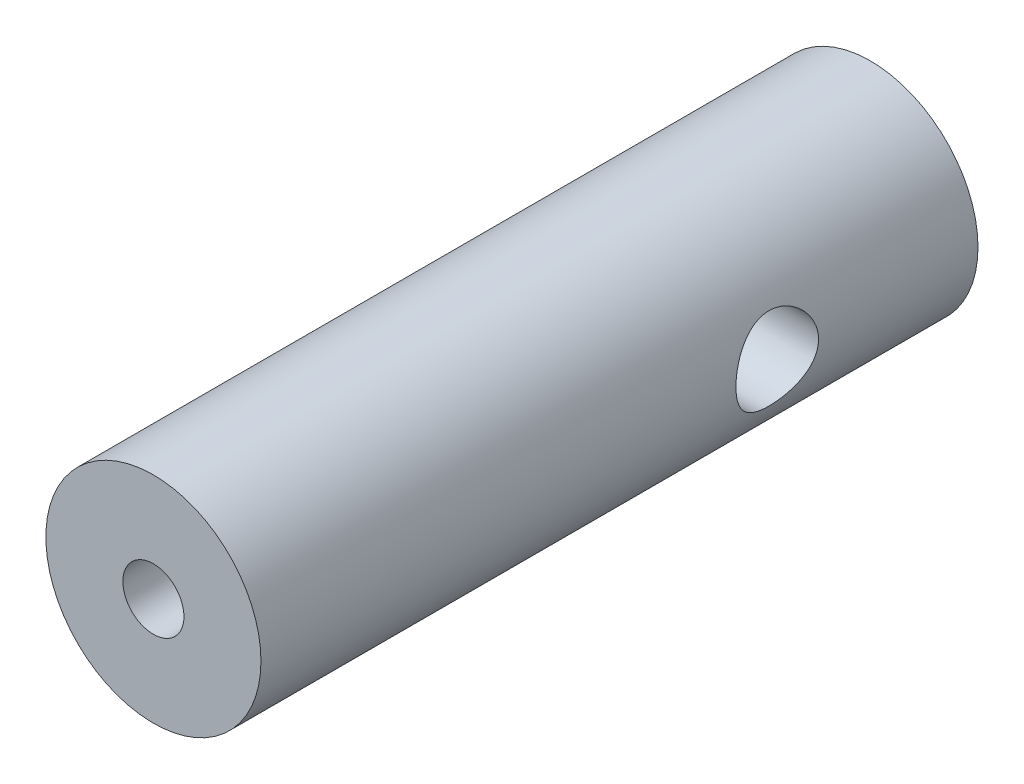
SolidWorks part; units mm, degrees
ref_plane "Front Plane" through (0, 0, 0) normal (0, 0, 1) x (1, 0, 0)
ref_plane "Top Plane" through (0, 0, 0) normal (0, 1, 0) x (1, 0, 0)
ref_plane "Right Plane" through (0, 0, 0) normal (1, 0, 0) x (0, 0, -1)
sketch "Sketch1" plane through (0, 0, 0) normal (0, 0, 1) x (1, 0, 0)
  circle A0 centre (0, 0) radius 4.7625
  dimension "D1" = 9.525
extrude "Boss-Extrude1" add sketch "Sketch1" along normal blind 31.75
sketch "Sketch2" plane through (0, 0, 31.75) normal (0, 0, 1) x (1, 0, 0)
  circle A0 centre (0, 0) radius 1.905
  dimension "D1" = 3.81
extrude "Cut-Extrude1" [suppressed] cut sketch "Sketch2" against normal blind 12.7
sketch "Sketch3" plane through (0, 0, 0) normal (1, 0, 0) x (0, 0, -1)
  line L0 (-31.75, 4.7625) -> (-31.75, -4.7625) construction
  circle A0 centre (-8.89, 0) radius 1.8288
  dimension "D2" = 3.6576
  dimension "D1" = 22.86
extrude "Cut-Extrude2" cut sketch "Sketch3" against normal through all and the other way through all
hole_wizard "#6-32 Tapped Hole1" positions "Sketch5" profile "Sketch6" tap size "#6-32" standard "ANSI Inch"
sketch "Sketch5" plane through (0, 0, 31.75) normal (0, 0, 1) x (1, 0, 0)
  point P0 (0, 0)
sketch "Sketch6" plane through (0, 0, 31.75) normal (1, 0, 0) x (0, -1, 0)
  line L0 (0, 0) -> (0, 13.5127)
  line L1 (0, 13.5127) -> (1.3525, 12.7)
  line L2 (1.3525, 12.7) -> (1.3525, 0)
  line L5 (1.3525, 0) -> (0, 0)
  line L10 (0, 13.5127) -> (-1.3526, 12.7) construction
  line L11 (0, -6.35) -> (0, 107.95) construction
  dimension "Tap Drill Dia." = 2.7051
  dimension "Tap Drill Depth" = 12.7
  dimension "Drill Angle" = 118
cosmetic thread "Hole Thread1" parameters "D1"=1.0644, "D2"=3.5052
